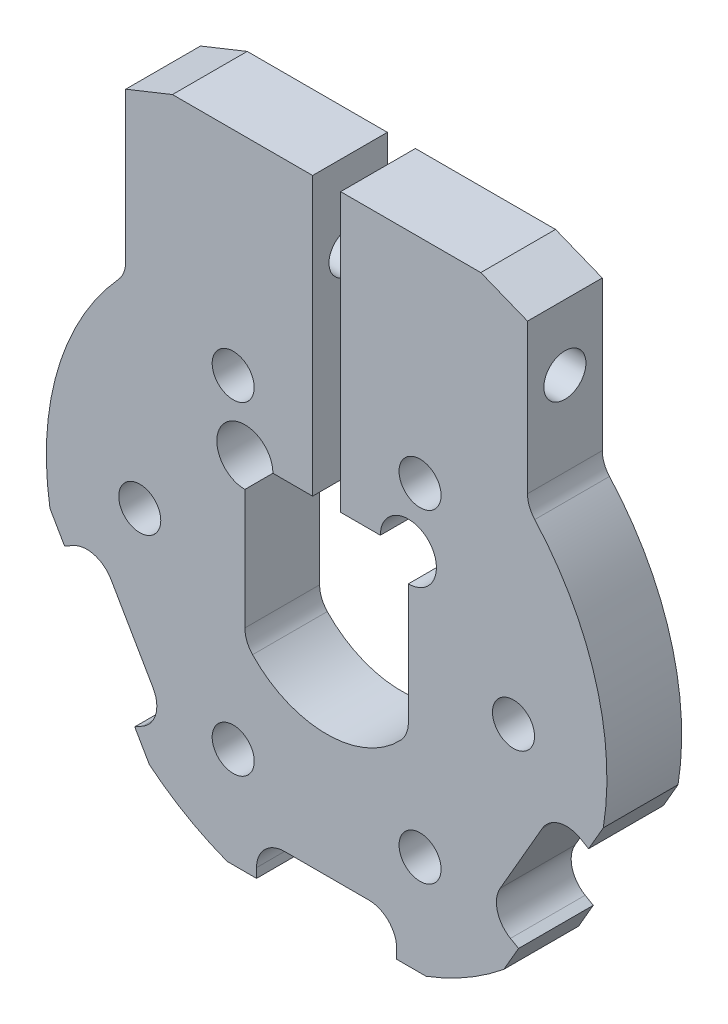
SolidWorks part; units mm, degrees
material "7075-T6 (SN)"
ref_plane "Ebene vorne" through (0, 0, 0) normal (0, 0, 1) x (1, 0, 0)
ref_plane "Ebene oben" through (0, 0, 0) normal (0, 1, 0) x (1, 0, 0)
ref_plane "Ebene rechts" through (0, 0, 0) normal (1, 0, 0) x (0, 0, -1)
sketch "Skizze1" plane through (0, 0, 0) normal (0, 0, 1) x (1, 0, 0)
  line L0 (4.5, -24.0474) -> (-4.5, -24.0474)
  line L1 (-7.5, -27.0474) -> (-7.5, -28.0474)
  line L2 (-7.5, -28.0474) -> (-10.6463, -28.0474)
  line L3 (-18.9666, -23.2437) -> (-20.5397, -20.5189)
  line L4 (-20.5397, -20.5189) -> (-19.6737, -20.0189)
  line L5 (-18.5756, -15.9208) -> (-23.0756, -8.1266)
  line L6 (-27.1737, -7.0285) -> (-28.0397, -7.5285)
  line L7 (-28.0397, -7.5285) -> (-29.6129, -4.8037)
  line L8 (-21.5, 22.1077) -> (-21.5, 38.1077)
  line L9 (-21.5, 38.1077) -> (-16.5, 40.1077)
  line L10 (-16.5, 40.1077) -> (-1.5, 40.1077)
  line L11 (-1.5, 40.1077) -> (-1.5, 10.3831)
  line L12 (-1.5, 10.3831) -> (-5.75, 10.3831)
  line L13 (-8.75, 7.3831) -> (-8.75, -5.4593)
  line L14 (8.75, -5.4593) -> (8.75, 7.3831)
  line L15 (5.75, 10.3831) -> (1.5, 10.3831)
  line L16 (1.5, 10.3831) -> (1.5, 40.1077)
  line L17 (1.5, 40.1077) -> (16.5, 40.1077)
  line L18 (16.5, 40.1077) -> (21.5, 38.1077)
  line L19 (21.5, 38.1077) -> (21.5, 22.1077)
  line L20 (29.6129, -4.8037) -> (28.0397, -7.5285)
  line L21 (28.0397, -7.5285) -> (27.1737, -7.0285)
  line L22 (23.0756, -8.1266) -> (18.5756, -15.9208)
  line L23 (19.6737, -20.0189) -> (20.5397, -20.5189)
  line L24 (20.5397, -20.5189) -> (18.9666, -23.2437)
  line L25 (10.6463, -28.0474) -> (7.5, -28.0474)
  line L26 (7.5, -28.0474) -> (7.5, -27.0474)
  line L27 (0, 48.7795) -> (0, -48.7795) construction
  line L28 (-5.75, 10.3831) -> (-8.75, 10.3831) construction
  line L29 (-8.75, 10.3831) -> (-8.75, 7.3831) construction
  line L30 (5.75, 10.3831) -> (8.75, 10.3831) construction
  line L31 (8.75, 10.3831) -> (8.75, 7.3831) construction
  line L32 (-20.8256, -12.0237) -> (0, 0) construction
  line L33 (0, 0) -> (20.8256, -12.0237) construction
  arc A6 (-4.5, -24.0474) -> (-7.5, -27.0474) centre (-4.5, -27.0474) ccw
  arc A7 (-18.9666, -23.2437) -> (-10.6463, -28.0474) centre (0, 0) ccw
  arc A8 (-19.6737, -20.0189) -> (-18.5756, -15.9208) centre (-21.1737, -17.4208) ccw
  arc A9 (-23.0756, -8.1266) -> (-27.1737, -7.0285) centre (-25.6737, -9.6266) ccw
  arc A10 (-22.2727, 20.0979) -> (-29.6129, -4.8037) centre (0, 0) ccw
  arc A11 (-22.2727, 20.0979) -> (-21.5, 22.1077) centre (-24.5, 22.1077) ccw
  arc A12 (-5.75, 10.3831) -> (-8.75, 7.3831) centre (-8.75, 10.3831) ccw
  arc A13 (-8.75, -5.4593) -> (-7.9256, -7.525) centre (-5.75, -5.4593) ccw
  arc A14 (-7.9256, -7.525) -> (7.9256, -7.525) centre (0, 0) ccw
  arc A15 (7.9256, -7.525) -> (8.75, -5.4593) centre (5.75, -5.4593) ccw
  arc A16 (8.75, 7.3831) -> (5.75, 10.3831) centre (8.75, 10.3831) ccw
  arc A17 (21.5, 22.1077) -> (22.2727, 20.0979) centre (24.5, 22.1077) ccw
  arc A18 (29.6129, -4.8037) -> (22.2727, 20.0979) centre (0, 0) ccw
  arc A19 (27.1737, -7.0285) -> (23.0756, -8.1266) centre (25.6737, -9.6266) ccw
  arc A20 (18.5756, -15.9208) -> (19.6737, -20.0189) centre (21.1737, -17.4208) ccw
  arc A21 (10.6463, -28.0474) -> (18.9666, -23.2437) centre (0, 0) ccw
  arc A22 (7.5, -27.0474) -> (4.5, -24.0474) centre (4.5, -27.0474) ccw
  circle A23 centre (0, 0) radius 30 construction
  point P0 (0, -24.0474)
  point P3 (0, 0)
  point P5 (0, 0)
  point P7 (0, 0)
  point P9 (0, 0)
  point P10 (0, 0)
  point P11 (0, 0)
  point P73 (0, 0)
  point P74 (0, 0)
  point P75 (0, 0)
  point P76 (0, 0)
  point P77 (0, 0)
  point P78 (0, 0)
  point P79 (0, 0)
  point P80 (0, 0)
  point P81 (0, 0)
  point P82 (0, 0)
  point P83 (0, 0)
  point P84 (0, 0)
  point P85 (0, 0)
  point P87 (0, 0)
  point P88 (-8.75, 8.3308)
  dimension "D10" = 10.9289
  dimension "D12" = 3
  dimension "D13" = 60
  dimension "D1" = 43
  dimension "D2" = 3
  dimension "D3" = 5
  dimension "D4" = 2
  dimension "D5" = 9
  dimension "D6" = 3.1463
  dimension "D7" = 4
  dimension "D9" = 17.5
  dimension "D11" = 10.3831
  dimension "D14" = 60
  dimension "D16" = 18
  dimension "D17" = 4
  dimension "D18" = 4
extrude "Aufsatz-Linear austragen1" add sketch "Skizze1" along normal blind 8
hole_wizard "Durchgangsloch für M41" positions "Skizze2" profile "Skizze3" hole size "M4" standard "DIN" end condition through all
sketch "Skizze2" plane through (21.5, 0, 0) normal (1, 0, 0) x (0, 0, -1)
  line L0 (-4, 40.1077) -> (-4, 22.1077) construction
  line L1 (-8, 40.1077) -> (0, 40.1077) construction
  point P0 (-4, 31.1077)
  point P11 (0, 0)
  point P12 (-4, 31.1077)
  point P13 (0, 0)
  point P14 (0, 0)
  point P17 (0, 0)
  dimension "D1" = 18
sketch "Skizze3" plane through (21.5, 31.1077, 4) normal (0, 1, 0) x (0, 0, -1)
  line L0 (0, 0) -> (0, 51.5)
  line L1 (0, 51.5) -> (2.25, 51.5)
  line L2 (2.25, 51.5) -> (2.25, 0)
  line L5 (2.25, 0) -> (0, 0)
  line L11 (0, -6.35) -> (0, 107.95) construction
  dimension "Bohrerdurchmesser" = 4.5
  dimension "Bohrungstiefe" = 51.5
hole_wizard "Durchgangsloch für M42" positions "Skizze6" profile "Skizze7" hole size "M4" standard "DIN" end condition through all
sketch "Skizze6" plane through (0, 0, 8) normal (0, 0, 1) x (1, 0, 0)
  line L0 (0, -24.0474) -> (0, 34.4221) construction
  line L1 (-4.5, -24.0474) -> (4.5, -24.0474) construction
  line L3 (0, 0) -> (-10, 17.3205) construction
  arc A0 (-7.9256, -7.525) -> (7.9256, -7.525) centre (0, 0) ccw construction
  arc A1 (-7.9256, -7.525) -> (7.9256, -7.525) centre (0, 0) ccw
  circle A2 centre (0, 0) radius 20 construction
  point P15 (-10, 17.3205)
  point P46 (10, 17.3205)
  point P47 (20, 0)
  point P48 (10, -17.3205)
  point P49 (-10, -17.3205)
  point P50 (-20, 0)
  dimension "D1" = 40
  dimension "D2" = 30
  dimension "D3" = 6
sketch "Skizze7" plane through (-20, 0, 8) normal (1, 0, 0) x (0, -1, 0)
  line L0 (0, 0) -> (0, 8)
  line L1 (0, 8) -> (2.25, 8)
  line L2 (2.25, 8) -> (2.25, 0)
  line L5 (2.25, 0) -> (0, 0)
  line L11 (0, -6.35) -> (0, 107.95) construction
  dimension "Bohrerdurchmesser" = 4.5
  dimension "Bohrungstiefe" = 8
